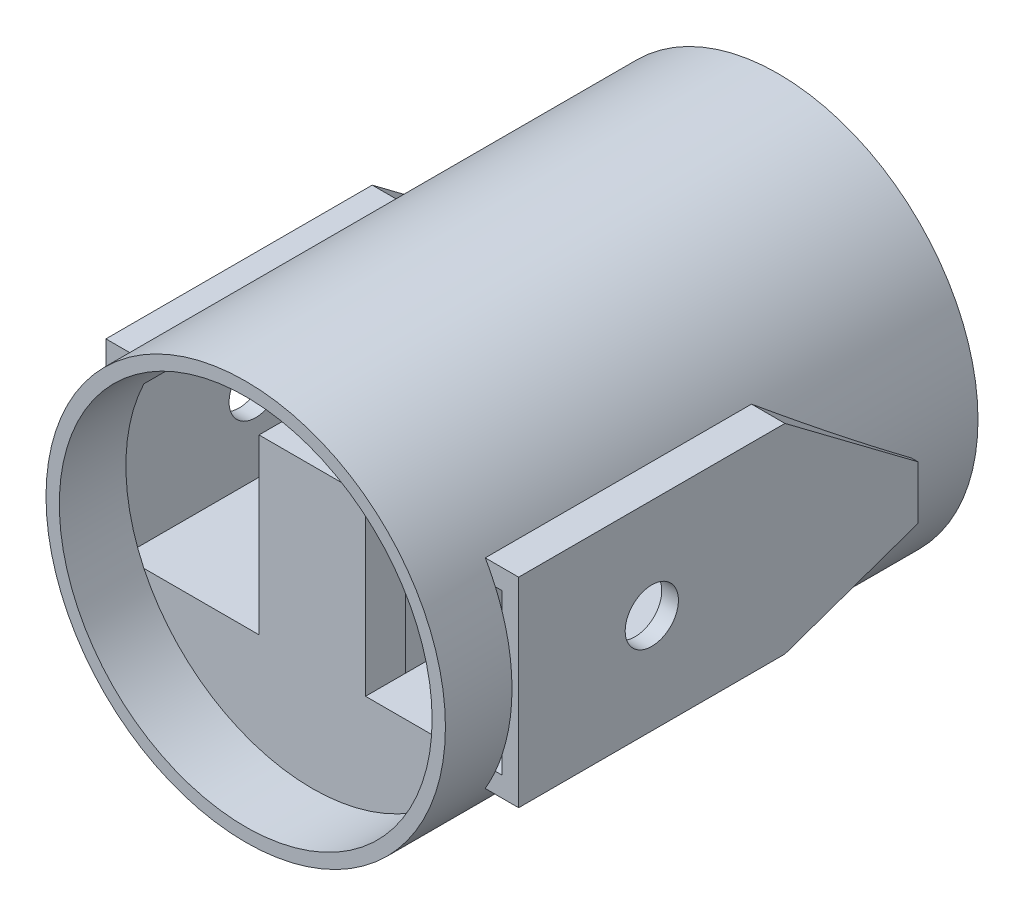
SolidWorks part; units mm, degrees
ref_plane "Alzado" through (0, 0, 0) normal (0, 0, 1) x (1, 0, 0)
ref_plane "Planta" through (0, 0, 0) normal (0, 1, 0) x (1, 0, 0)
ref_plane "Vista lateral" through (0, 0, 0) normal (1, 0, 0) x (0, 0, -1)
sketch "Croquis1" plane through (0, 0, 0) normal (0, 0, 1) x (1, 0, 0)
  line L0 (-12.6491, -6) -> (-4, -6)
  line L2 (-4, -14.4568) -> (-4, -13.4164)
  line L4 (4, -14.4568) -> (4, -13.4164)
  line L5 (-4, -13.4164) -> (-4, -6)
  line L6 (4, -6) -> (12.6491, -6)
  line L7 (-14.25, 6) -> (-12.6491, 6)
  line L8 (-14.25, 6) -> (-14.25, -6)
  line L9 (-14.25, -6) -> (-12.6491, -6)
  line L10 (14.25, 6) -> (14.25, -6)
  line L11 (4, -6) -> (4, -13.4164)
  line L13 (-15.5, 7.5) -> (-12.9904, 7.5)
  line L14 (-15.5, 7.5) -> (-15.5, -7.5)
  line L15 (-15.5, -7.5) -> (-12.9904, -7.5)
  line L16 (15.5, 7.5) -> (15.5, -7.5)
  line L18 (12.6491, -6) -> (14.25, -6)
  line L20 (12.6491, 6) -> (14.25, 6)
  line L21 (12.9904, -7.5) -> (15.5, -7.5)
  line L22 (12.9904, 7.5) -> (15.5, 7.5)
  arc A2 (4, -14.4568) -> (12.9904, -7.5) centre (0, 0) ccw
  arc A4 (-12.9904, -7.5) -> (-4, -14.4568) centre (0, 0) ccw
  arc A5 (12.9904, 7.5) -> (-12.9904, 7.5) centre (0, 0) ccw
  arc A7 (12.6491, 6) -> (-12.6491, 6) centre (0, 0) ccw
  point P4 (0, -14)
  dimension "D4" = 28.5
  dimension "D3" = 12
  dimension "D5" = 31
  dimension "D6" = 15
extrude "Saliente-Extruir1" add sketch "Croquis1" along normal blind 10 and the other way blind 10
sketch "Croquis2" plane through (-15.5, 0, 0) normal (-1, 0, 0) x (0, 0, 1)
  line L0 (-10, 7.5) -> (10, -7.5) construction
  line L1 (10, -7.5) -> (10, 7.5) construction
  line L2 (10, 7.5) -> (-10, -7.5) construction
  circle A0 centre (0, 0) radius 2
  dimension "D1" = 4
extrude "Cortar-Extruir1" cut sketch "Croquis2" against normal up to surface (31 mm away) up to face at (15.5, 0, 0)
sketch "Croquis3" plane through (-15.5, 0, 0) normal (-1, 0, 0) x (0, 0, 1)
  line L0 (0, 0) -> (-10, 0) construction
  line L1 (-10, 7.5) -> (-10, -7.5) construction
  line L2 (-20, -4) -> (-10, -7.5)
  line L4 (-20, -4) -> (-20, 0)
  line L5 (-20, 0) -> (-10, 0)
  line L6 (-10, -4) -> (-10, 0)
  line L7 (-20, -4) -> (-10, 0) construction
  line L8 (-20, 0) -> (-10, -4) construction
  line L9 (-10, -7.5) -> (-10, -4)
  point P5 (-15, -2)
  dimension "D1" = 10
  dimension "D2" = 4
  dimension "D3" = 10
extrude "Saliente-Extruir2" add sketch "Croquis3" against normal up to surface (31 mm away) up to face at (15.5, 0, -2)
sketch "Croquis4" plane through (0, 0, -20) normal (0, 0, -1) x (-1, 0, 0)
  line L0 (-15.5, 0) -> (15.5, 0) construction
  circle A0 centre (0, 0) radius 14
  circle A1 centre (0, 0) radius 15
  dimension "D1" = 28
  dimension "D2" = 30
extrude "Saliente-Extruir3" add sketch "Croquis4" against normal blind 10
sketch "Croquis5" plane through (15.5, 0, 0) normal (1, 0, 0) x (0, 0, -1)
  line L0 (10, 7.5) -> (10, 0)
  line L1 (10, 0) -> (10, 7.5) construction
  line L2 (10, 0) -> (20, 0)
  line L3 (20, 0) -> (10, 7.5)
extrude "Saliente-Extruir4" add sketch "Croquis5" against normal up to surface (31 mm away) up to face at (-15.5, -2, 0)
sketch "Croquis6" plane through (0, 0, -20) normal (0, 0, -1) x (-1, 0, 0)
  line L0 (-14, 0) -> (14, 0) construction
  line L1 (-14, 0) -> (14, 0)
  arc A0 (14, 0) -> (-14, 0) centre (0, 0) ccw
extrude "Cortar-Extruir3" cut sketch "Croquis6" against normal up to surface (30 mm away) up to face at (0, -0.8435, 10)
sketch "Croquis7" plane through (0, 0, -20) normal (0, 0, -1) x (-1, 0, 0)
  line L0 (-14, 0) -> (14, 0) construction
  line L1 (-13.4164, -4) -> (13.4164, -4)
  line L2 (-13.4164, -4) -> (13.4164, -4) construction
  arc A0 (-13.4164, -4) -> (13.4164, -4) centre (0, 0) ccw
extrude "Saliente-Extruir5" add sketch "Croquis7" against normal up to surface (10 mm away) up to face at (0, -1.2375, -10)
sketch "Croquis8" plane through (0, 0, -10) normal (0, 0, 1) x (1, 0, 0)
  line L0 (-14, 0) -> (14, 0) construction
  line L1 (-14, 0) -> (-4, 0)
  line L3 (-12.6491, -6) -> (-4, -6)
  line L4 (-4, 0) -> (-4, -6)
  line L5 (14, 0) -> (4, 0)
  line L7 (12.6491, -6) -> (4, -6)
  line L8 (4, 0) -> (4, -6)
  arc A0 (-14, 0) -> (-12.6491, -6) centre (0, 0) ccw
  arc A1 (12.6491, -6) -> (14, 0) centre (0, 0) ccw
extrude "Cortar-Extruir5" cut sketch "Croquis8" against normal up to surface (10 mm away) up to face at (0, 7, -20)
sketch "Croquis9" plane through (0, 0, 10) normal (0, 0, 1) x (1, 0, 0)
  line L0 (-13.7477, -6) -> (-4, -6)
  line L1 (-4, -6) -> (-14.25, -6) construction
  line L2 (14.25, -6) -> (4, -6) construction
  line L3 (4, -6) -> (13.7477, -6)
  line L9 (-4, 14) -> (4, 14)
  line L10 (-4, 14) -> (-4, -6)
  line L15 (0, 0) -> (0.7506, -2.6692) construction
  line L17 (4, 14) -> (4, -6)
  line L18 (-4, 14) -> (0, 0) construction
  line L19 (0, 0) -> (4, 14) construction
  arc A0 (-13.7477, -6) -> (13.7477, -6) centre (0, 0) ccw
  point P1 (0, -6)
  dimension "D1" = 14
  dimension "D2" = 8
extrude "Saliente-Extruir6" add sketch "Croquis9" against normal blind 3
ref_axis "Eje1" through (18.5095, 0, 0) along (-1, 0, 0)
sketch "Croquis10" plane through (0, 0, 10) normal (0, 0, 1) x (1, 0, 0)
  line L0 (4, -6) -> (4, 13.4164) construction
  line L1 (-4, 11) -> (4, 11)
  line L2 (-4, 11) -> (-4, 5)
  line L3 (-4, 5) -> (4, 5)
  line L4 (4, 11) -> (4, 5)
  line L5 (-4, 11) -> (4, 5) construction
  line L6 (-4, 5) -> (4, 11) construction
  line L7 (18.5095, 0) -> (-15.5, 0) construction
  point P0 (0, 8)
  dimension "D1" = 5
  dimension "D2" = 6
extrude "Saliente-Extruir7" add sketch "Croquis10" against normal blind 5
sketch "Croquis11" plane through (0, 0, 10) normal (0, 0, 1) x (1, 0, 0)
  line L0 (4, -6) -> (4, 13.4164) construction
  line L1 (-4, 9) -> (4, 9)
  line L2 (-4, 9) -> (-4, 7)
  line L3 (-4, 7) -> (4, 7)
  line L4 (4, 9) -> (4, 7)
  line L5 (-4, 9) -> (4, 7) construction
  line L6 (-4, 7) -> (4, 9) construction
  point P0 (0, 8)
  dimension "D1" = 2
  dimension "D2" = 2
extrude "Cortar-Extruir6" cut sketch "Croquis11" against normal blind 3
sketch "Croquis12" plane through (0, 0, 10) normal (0, 0, 1) x (1, 0, 0)
  circle A0 centre (0, 0) radius 15
  circle A1 centre (0, 0) radius 14
extrude "Saliente-Extruir8" add sketch "Croquis12" along normal blind 5
sketch "Croquis13" plane through (0, 0, -20) normal (0, 0, -1) x (-1, 0, 0)
  line L0 (-4, 0) -> (4, 0) construction
  circle A0 centre (0, 0) radius 15
  circle A1 centre (0, 0) radius 14
extrude "Saliente-Extruir9" add sketch "Croquis13" along normal blind 5
